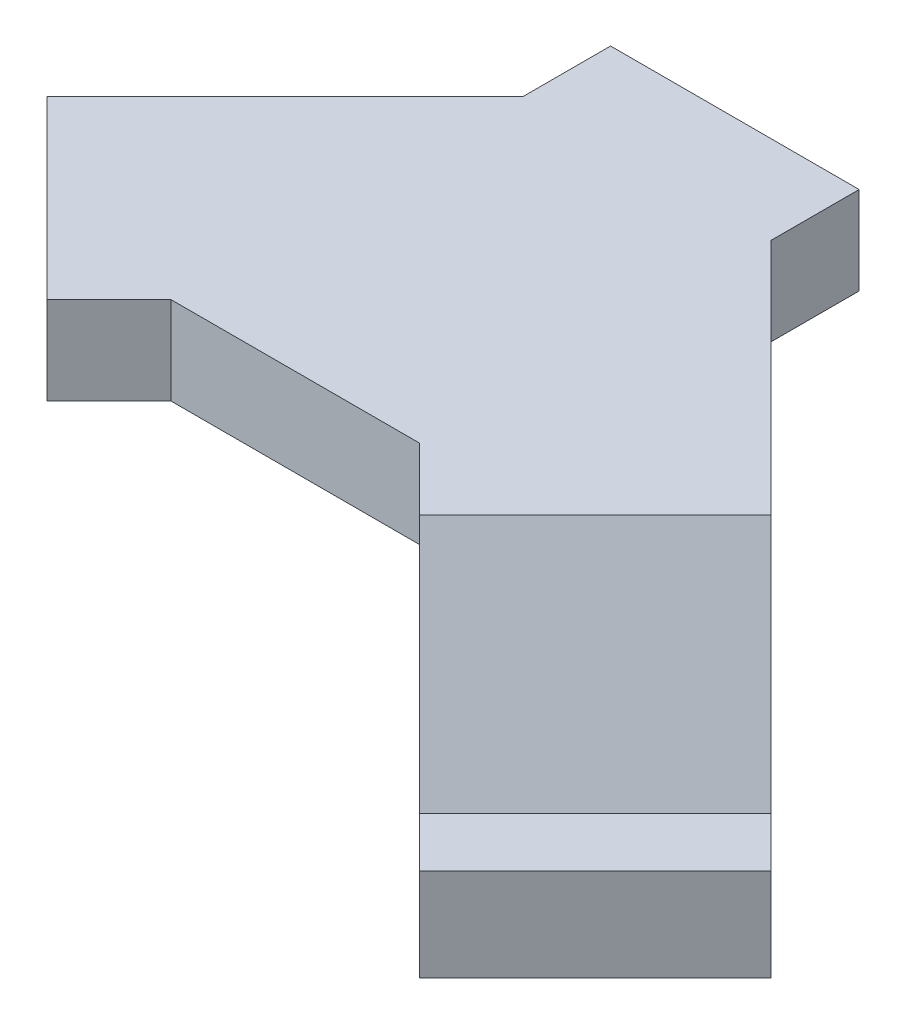
SolidWorks part; units mm, degrees
ref_plane "Front Plane" through (0, 0, 0) normal (0, 0, 1) x (1, 0, 0)
ref_plane "Top Plane" through (0, 0, 0) normal (0, 1, 0) x (1, 0, 0)
ref_plane "Right Plane" through (0, 0, 0) normal (1, 0, 0) x (0, 0, -1)
sketch "Sketch1" plane through (0, 0, 0) normal (0, 1, 0) x (1, 0, 0)
  line L0 (-169.095, -181.1878) -> (-159.095, -171.1878) construction
  line L1 (-207.0239, -121.1878) -> (-217.0239, -111.1878)
  line L2 (-217.0239, -111.1878) -> (-231.1661, -111.1878)
  line L3 (-231.1661, -111.1878) -> (-241.1661, -121.1878)
  line L4 (-241.1661, -121.1878) -> (-231.1661, -131.1878)
  line L5 (-231.1661, -131.1878) -> (-217.0239, -131.1878)
  line L6 (-217.0239, -131.1878) -> (-207.0239, -121.1878)
  line L7 (-279.095, -181.1878) -> (-289.095, -171.1878) construction
  line L8 (-279.095, -181.1878) -> (-169.095, -181.1878) construction
  line L9 (-279.095, -61.1878) -> (-169.095, -61.1878) construction
  line L10 (-224.095, -111.1878) -> (-224.095, -131.1878) construction
  point P1 (-224.095, -121.1878)
  point P10 (0, 0)
extrude "Boss-Extrude1" add sketch "Sketch1" along normal blind 5
sketch "Sketch2" plane through (0, 5, 0) normal (0, 1, 0) x (1, 0, 0)
  line L0 (-231.1661, -131.1878) -> (-241.1661, -121.1878)
  line L1 (-231.1661, -106.1878) -> (-217.0239, -106.1878)
  line L2 (-231.1661, -106.1878) -> (-231.1661, -111.1878)
  line L3 (-231.1661, -111.1878) -> (-217.0239, -111.1878)
  line L4 (-217.0239, -106.1878) -> (-217.0239, -111.1878)
  line L5 (-231.1661, -106.1878) -> (-217.0239, -111.1878) construction
  line L6 (-231.1661, -111.1878) -> (-217.0239, -106.1878) construction
  line L7 (-231.1661, -131.1878) -> (-234.7016, -134.7234)
  line L8 (-241.1661, -121.1878) -> (-244.7016, -124.7234)
  line L9 (-234.7016, -134.7234) -> (-244.7016, -124.7234)
  line L15 (-217.0239, -131.1878) -> (-207.0239, -121.1878)
  line L16 (-217.0239, -131.1878) -> (-213.4884, -134.7234)
  line L18 (-207.0239, -121.1878) -> (-203.4884, -124.7234)
  line L19 (-213.4884, -134.7234) -> (-203.4884, -124.7234)
  point P0 (-224.095, -108.6878)
  dimension "D1" = 5
extrude "Boss-Extrude2" add sketch "Sketch2" against normal up to surface (5 mm away) up to face at (-224.095, 0, 121.1878)
sketch "Sketch3" plane through (-164.1059, 0, 164.1059) normal (0.7071, 0, -0.7071) x (-0.7071, 0, -0.7071)
  line L0 (55.6953, 5) -> (-4.5509, 30.8948)
  line L1 (-4.5509, 30.8948) -> (-4.5509, 32.8948)
  line L2 (-4.5509, 32.8948) -> (-8.5509, 32.8948)
  line L3 (-8.5509, 32.8948) -> (-8.5509, 27.6141)
  line L4 (-8.5509, 27.6141) -> (55.6953, 0)
  line L5 (55.6953, 0) -> (55.6953, 5)
  dimension "D1" = 4
  dimension "D2" = 2
extrude "Boss-Extrude3" add sketch "Sketch3" against normal up to vertex (14.1421 mm away) up to point (-213.4884, 0, 134.7234)
ref_plane "Plane2" through (-224.095, 0, 0) normal (1, 0, 0) x (0, 0, -1)
mirror "Mirror1" about plane through (-224.095, 0, 0) normal (1, 0, 0) rebuild error yes
